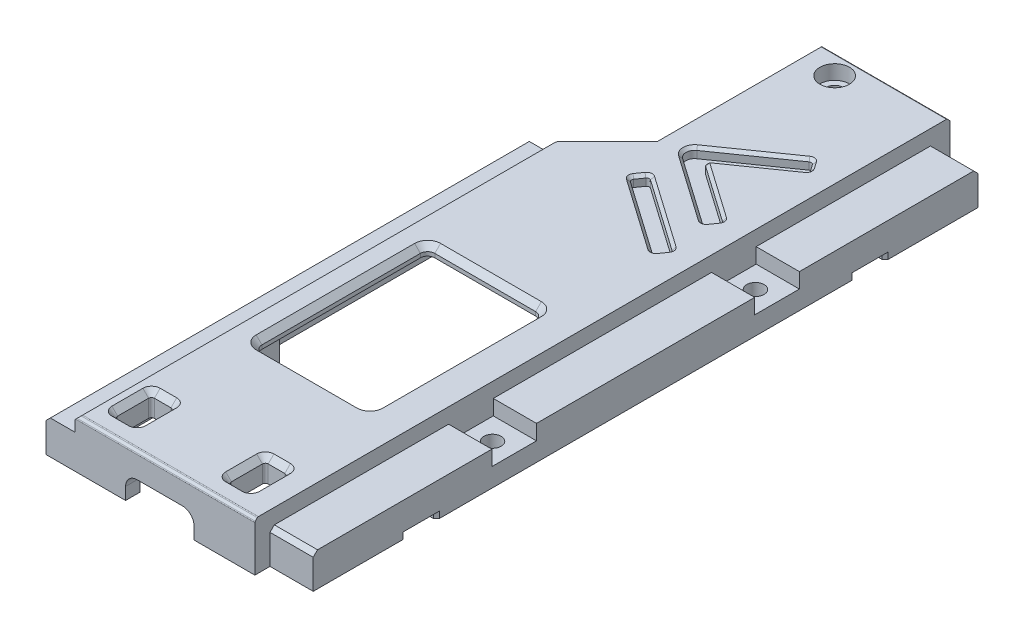
SolidWorks part; units mm, degrees
ref_plane "前视基准面" through (0, 0, 0) normal (0, 0, 1) x (1, 0, 0)
ref_plane "上视基准面" through (0, 0, 0) normal (0, 1, 0) x (1, 0, 0)
ref_plane "右视基准面" through (0, 0, 0) normal (1, 0, 0) x (0, 0, -1)
sketch "草图1" plane through (0, 0, 0) normal (0, 1, 0) x (1, 0, 0)
  line L1 (0, 0) -> (35, 0)
  line L2 (0, 0) -> (0, 96.5)
  line L3 (0, 96.5) -> (35, 96.5)
  line L4 (35, 0) -> (35, 96.5)
  point P1 (35, 96.5)
  dimension "D1" = 35
  dimension "D2" = 96.5
extrude "凸台-拉伸1" add sketch "草图1" along normal blind 6.8
sketch "草图10" plane through (0, 0, 0) normal (0, -1, 0) x (1, 0, 0)
  line L0 (3, -57.9) -> (3, -27)
  line L2 (3, -27) -> (5.4, -27)
  line L3 (3, -20) -> (3, -2)
  line L9 (26.2, -2) -> (3, -2)
  line L10 (5.4, -20) -> (5.4, -27)
  line L11 (3, -57.9) -> (26.2, -57.9)
  line L12 (3, -20) -> (5.4, -20)
  line L17 (26.2, -57.9) -> (26.2, -2)
  line L18 (0, 0) -> (35, 0) construction
  line L19 (3, -69.8559) -> (28.6, -69.8559) construction
  line L20 (3, -69.8559) -> (3, -2) construction
  line L21 (3, -2) -> (28.6, -2) construction
  line L22 (28.6, -69.8559) -> (28.6, -2) construction
  line L23 (0, -96.5) -> (0, 0) construction
  dimension "D2" = 2.4
  dimension "D3" = 55.9
  dimension "D4" = 18
  dimension "D5" = 25
  dimension "D7" = 2
  dimension "D8" = 25.6
  dimension "D9" = 3
  dimension "D1" = 2.4
extrude "切除-拉伸6" cut sketch "草图10" against normal blind 3.4
sketch "草图11" plane through (0, 0, 0) normal (0, 0, 1) x (1, 0, 0)
  line L0 (0, 0) -> (47, 0) construction
  line L1 (11.05, 0) -> (20.55, 0)
  line L2 (11.05, 0) -> (11.05, 1.7)
  line L3 (12.65, 3.3) -> (18.95, 3.3)
  line L4 (20.55, 1.7) -> (20.55, 0)
  line L7 (0, 6.8) -> (0, 0) construction
  arc A0 (18.95, 3.3) -> (20.55, 1.7) centre (18.95, 1.7) cw
  arc A1 (11.05, 1.7) -> (12.65, 3.3) centre (12.65, 1.7) cw
  dimension "D4" = 1.6
  dimension "D1" = 9.5
  dimension "D2" = 3.3
  dimension "D3" = 11.05
extrude "切除-拉伸7" cut sketch "草图11" against normal up to next
sketch "草图13" plane through (0, 3.4, 0) normal (0, -1, 0) x (1, 0, 0)
  line L1 (7.8, -21.18) -> (23.8, -21.18)
  line L2 (7.8, -21.18) -> (7.8, -45.18)
  line L3 (7.8, -45.18) -> (23.8, -45.18)
  line L4 (23.8, -21.18) -> (23.8, -45.18)
  line L5 (0, 0) -> (35, 0) construction
  line L6 (0, -96.5) -> (0, 0) construction
  dimension "D1" = 7.8
  dimension "D2" = 16
  dimension "D3" = 24
  dimension "D4" = 21.18
extrude "切除-拉伸9" cut sketch "草图13" against normal blind 10
sketch "草图24" plane through (0, 6.8, 0) normal (0, 1, 0) x (1, 0, 0)
  line L0 (0, 0) -> (35, 0) construction
  line L1 (6.35, 8.3) -> (9.45, 8.3)
  line L2 (6.35, 8.3) -> (6.35, 3.2)
  line L3 (6.35, 3.2) -> (9.45, 3.2)
  line L4 (9.45, 8.3) -> (9.45, 3.2)
  line L5 (22.15, 8.3) -> (25.25, 8.3)
  line L6 (22.15, 8.3) -> (22.15, 3.2)
  line L7 (22.15, 3.2) -> (25.25, 3.2)
  line L8 (25.25, 8.3) -> (25.25, 3.2)
  line L12 (11.05, 2) -> (11.05, 0) construction
  line L13 (20.55, 2) -> (20.55, 0) construction
  dimension "D1" = 3.1
  dimension "D2" = 5.1
  dimension "D3" = 3.1
  dimension "D4" = 5.1
  dimension "D5" = 3.2
  dimension "D6" = 1.6
  dimension "D7" = 1.6
extrude "切除-拉伸17" cut sketch "草图24" against normal up to next
sketch "草图25" plane through (0, 3.4, 0) normal (0, -1, 0) x (1, 0, 0)
  line L0 (25.25, -8.3) -> (22.15, -8.3) construction
  line L1 (25.25, -3.2) -> (25.25, -8.3) construction
  line L2 (22.15, -3.2) -> (25.25, -3.2) construction
  line L3 (22.15, -8.3) -> (22.15, -3.2) construction
  line L4 (9.45, -8.3) -> (6.35, -8.3) construction
  line L5 (9.45, -3.2) -> (9.45, -8.3) construction
  line L6 (6.35, -3.2) -> (9.45, -3.2) construction
  line L7 (6.35, -8.3) -> (6.35, -3.2) construction
  line L8 (25.25, -8.3) -> (22.15, -8.3)
  line L9 (25.25, -3.2) -> (25.25, -8.3)
  line L10 (22.15, -3.2) -> (25.25, -3.2)
  line L11 (22.15, -8.3) -> (22.15, -3.2)
  line L12 (9.45, -8.3) -> (6.35, -8.3)
  line L13 (9.45, -3.2) -> (9.45, -8.3)
  line L14 (6.35, -3.2) -> (9.45, -3.2)
  line L15 (6.35, -8.3) -> (6.35, -3.2)
  line L16 (26.45, -9.5) -> (20.95, -9.5)
  line L17 (20.95, -9.5) -> (20.95, -2)
  line L18 (20.95, -2) -> (26.45, -2)
  line L19 (26.45, -2) -> (26.45, -9.5)
  line L20 (10.65, -9.5) -> (5.15, -9.5)
  line L21 (5.15, -9.5) -> (5.15, -2)
  line L22 (5.15, -2) -> (10.65, -2)
  line L23 (10.65, -2) -> (10.65, -9.5)
  dimension "D1" = 1.2
extrude "切除-拉伸21" cut sketch "草图25" against normal blind 0.18 and the other way through all
fillet "圆角3" radius 0.4 8 edges at (25.25, 5.19, -8.3) (25.25, 5.19, -3.2) (22.15, 5.19, -3.2) (22.15, 5.19, -8.3) (9.45, 5.19, -8.3) (9.45, 5.19, -3.2) (6.35, 5.19, -3.2) (6.35, 5.19, -8.3)
chamfer "倒角2" distance 0.8 angle 45 16 edges at (25.25, 6.8, -5.75) (25.1328, 6.8, -8.1828) (25.1328, 6.8, -3.3172) (23.7, 6.8, -8.3) (23.7, 6.8, -3.2) (22.2672, 6.8, -8.1828) (22.2672, 6.8, -3.3172) (22.15, 6.8, -5.75) (9.45, 6.8, -5.75) (9.3328, 6.8, -8.1828) (9.3328, 6.8, -3.3172) (7.9, 6.8, -8.3) (7.9, 6.8, -3.2) (6.4672, 6.8, -8.1828) (6.4672, 6.8, -3.3172) (6.35, 6.8, -5.75)
fillet "圆角4" radius 1 4 edges at (23.8, 5.1, -21.18) (23.8, 5.1, -45.18) (7.8, 5.1, -45.18) (7.8, 5.1, -21.18)
chamfer "倒角1" distance 0.8 angle 45 8 edges at (15.8, 6.8, -45.18) (23.8, 6.8, -33.18) (7.8, 6.8, -33.18) (15.8, 6.8, -21.18) (23.5071, 6.8, -44.8871) (8.0929, 6.8, -44.8871) (23.5071, 6.8, -21.4729) (8.0929, 6.8, -21.4729)
sketch "草图26" plane through (0, 6.8, 0) normal (0, 1, 0) x (1, 0, 0)
  line L0 (4, 66.5) -> (10.7071, 73.2071) construction
  line L1 (11, 73.9142) -> (11, 96.0172) construction
  line L2 (4, 66.5) -> (11, 73.5)
  line L3 (11, 73.5) -> (11, 96.5)
  line L4 (0, 96.5) -> (0, 0) construction
  line L5 (35, 96.5) -> (0, 96.5) construction
  line L6 (0, 96.5) -> (0, 66.5)
  line L7 (11, 96.5) -> (0, 96.5)
  line L8 (4, 66.5) -> (0, 66.5)
extrude "切除-拉伸18" cut sketch "草图26" against normal up to next
sketch "草图28" plane through (0, 6.8, 0) normal (0, 1, 0) x (1, 0, 0)
  line L1 (0, 0) -> (4, 0)
  line L2 (0, 0) -> (0, 66.5)
  line L3 (0, 66.5) -> (4, 66.5)
  line L4 (4, 0) -> (4, 66.5)
extrude "切除-拉伸19" cut sketch "草图28" against normal blind 2.1
fillet "圆角5" radius 1 1 edges at (4, 5.75, -66.5)
chamfer "倒角3" distance 0.6 angle 45 4 edges at (11, 6.8, -85) (7.6464, 6.8, -70.1464) (4, 6.8, -33.0429) (4.0761, 6.8, -66.4685)
sketch "草图29" plane through (0, 3.4, 0) normal (0, -1, 0) x (1, 0, 0)
  line L0 (26.1, -48.179) -> (26.1, -18.179)
  line L1 (23.6, -15.679) -> (8, -15.679)
  line L2 (5.5, -18.179) -> (5.5, -48.179)
  line L3 (8, -50.679) -> (23.6, -50.679)
  line L4 (23.6, -16.679) -> (8, -16.679)
  line L5 (25.1, -48.179) -> (25.1, -18.179)
  line L6 (8, -49.679) -> (23.6, -49.679)
  line L7 (6.5, -18.179) -> (6.5, -48.179)
  line L8 (23.6, -16.679) -> (8, -16.679) construction
  line L9 (25.1, -48.179) -> (25.1, -18.179) construction
  line L10 (8, -49.679) -> (23.6, -49.679) construction
  line L11 (6.5, -18.179) -> (6.5, -48.179) construction
  arc A0 (23.6, -50.679) -> (26.1, -48.179) centre (23.6, -48.179) ccw
  arc A1 (26.1, -18.179) -> (23.6, -15.679) centre (23.6, -18.179) ccw
  arc A2 (8, -15.679) -> (5.5, -18.179) centre (8, -18.179) ccw
  arc A3 (5.5, -48.179) -> (8, -50.679) centre (8, -48.179) ccw
  arc A4 (25.1, -18.179) -> (23.6, -16.679) centre (23.6, -18.179) ccw
  arc A5 (23.6, -49.679) -> (25.1, -48.179) centre (23.6, -48.179) ccw
  arc A6 (6.5, -48.179) -> (8, -49.679) centre (8, -48.179) ccw
  arc A7 (8, -16.679) -> (6.5, -18.179) centre (8, -18.179) ccw
  arc A8 (25.1, -18.179) -> (23.6, -16.679) centre (23.6, -18.179) ccw construction
  arc A9 (23.6, -49.679) -> (25.1, -48.179) centre (23.6, -48.179) ccw construction
  arc A10 (6.5, -48.179) -> (8, -49.679) centre (8, -48.179) ccw construction
  arc A11 (8, -16.679) -> (6.5, -18.179) centre (8, -18.179) ccw construction
  dimension "D1" = 0
  dimension "D2" = 1
extrude "切除-拉伸20" cut sketch "草图29" against normal blind 2.06
chamfer "倒角4" distance 0.6 angle 45 2 edges at (0, 4.7, -33.25) (11, 0, -85)
sketch "草图30" plane through (0, 0, 0) normal (0, -1, 0) x (1, 0, 0)
  line L0 (28.6, -68.5) -> (28.6, -88.5) construction
  line L1 (12.5, -88.5) -> (12.5, -67.9) construction
  line L2 (28.6, -57.9) -> (28.6, -88.5) construction
  line L3 (12.5, -88.5) -> (12.5, -76.5)
  line L5 (35, -96.5) -> (11.6, -96.5) construction
  line L12 (12.5, -76.5) -> (12.5, -88.5) construction
  line L15 (3, -57.9) -> (26.2, -57.9) construction
  line L16 (3, -57.9) -> (28.6, -57.9)
  line L17 (28.6, -88.5) -> (28.6, -57.9)
  line L19 (28.6, -88.5) -> (12.5, -88.5)
  line L21 (12.5, -76.5) -> (3, -76.5)
  line L22 (3, -76.5) -> (3, -57.9)
  point P3 (28.6, -88.3067)
  point P6 (0, 0)
  point P7 (0, 0)
  point P8 (0, 0)
  point P9 (14.1823, -76.5)
  point P11 (0, 0)
  point P12 (0, 0)
  point P13 (12.5, -90.5404)
  point P15 (12.5, -88.6133)
  point P19 (0, 0)
  point P21 (0, 0)
  point P22 (0, 0)
  point P23 (0, 0)
  dimension "D1" = 12
  dimension "D2" = 8
extrude "切除-拉伸22" cut sketch "草图30" against normal blind 4
sketch "草图31" plane through (0, 6.8, 0) normal (0, 1, 0) x (1, 0, 0)
  line L0 (24.5128, 59.7234) -> (25.66, 61.3617)
  line L1 (12.66, 59.7234) -> (25.66, 59.7234) construction
  line L2 (12.66, 59.7234) -> (12.66, 82) construction
  line L3 (12.66, 82) -> (25.66, 82) construction
  line L4 (25.66, 59.7234) -> (25.66, 82) construction
  line L5 (24.5128, 59.7234) -> (13.8639, 67.1799)
  line L6 (25.66, 61.3617) -> (15.011, 68.8182)
  line L7 (13.8639, 67.1799) -> (15.011, 68.8182)
  line L8 (24.5128, 66.7234) -> (13.6042, 74.3617)
  line L9 (13.6042, 74.3617) -> (24.5128, 82)
  line L10 (24.5128, 82) -> (25.66, 80.3617)
  line L11 (25.66, 80.3617) -> (17.0911, 74.3617)
  line L12 (17.0911, 74.3617) -> (25.66, 68.3617)
  line L13 (25.66, 68.3617) -> (24.5128, 66.7234)
  line L14 (35, 96.5) -> (11.6, 96.5) construction
  line L15 (4, 0) -> (4, 66.0858) construction
  dimension "D1" = 2
  dimension "D2" = 55
  dimension "D3" = 55
  dimension "D4" = 0
  dimension "D5" = 0
  dimension "D6" = 0
  dimension "D7" = 13
  dimension "D8" = 7
  dimension "D9" = 2
  dimension "D10" = 2
  dimension "D11" = 90
  dimension "D12" = 12
  dimension "D13" = 0
  dimension "D14" = 0
  dimension "D15" = 13
  dimension "D16" = 14.5
  dimension "D17" = 8.66
extrude "切除-拉伸23" cut sketch "草图31" against normal blind 1.4
fillet "圆角6" radius 0.4 9 edges at (25.66, 6.1, -61.3617) (24.5128, 6.1, -59.7234) (15.011, 6.1, -68.8182) (13.8639, 6.1, -67.1799) (25.66, 6.1, -80.3617) (24.5128, 6.1, -82) (25.66, 6.1, -68.3617) (24.5128, 6.1, -66.7234) (17.0911, 6.1, -74.3617)
fillet "圆角7" radius 1.2 1 edges at (13.6042, 6.1, -74.3617)
chamfer "倒角5" distance 0.4 angle 45 20 edges at (21.4457, 6.8, -77.4108) (25.4968, 6.8, -80.3905) (17.3885, 6.8, -74.3617) (25.0864, 6.8, -81.1808) (21.4457, 6.8, -71.3126) (24.4841, 6.8, -81.8368) (25.4968, 6.8, -68.3329) (19.5966, 6.8, -78.5576) (25.0864, 6.8, -67.5425) (14.4964, 6.8, -74.3617) (24.4841, 6.8, -66.8866) (19.5966, 6.8, -70.1658) (20.3355, 6.8, -65.0899) (15.0398, 6.8, -68.655) (25.4968, 6.8, -61.3329) (14.4374, 6.8, -67.999) (25.0864, 6.8, -60.5425) (14.027, 6.8, -67.2087) (24.4841, 6.8, -59.8866) (19.1884, 6.8, -63.4516)
sketch "草图32" plane through (35, 0, 0) normal (1, 0, 0) x (0, 0, -1)
  line L0 (96.5, 6.8) -> (96.5, 0) construction
  line L1 (0, 6.8) -> (96.5, 6.8) construction
  line L2 (0, 6.8) -> (0, 0) construction
  line L3 (96.5, 6.8) -> (96.5, 0)
  line L4 (0, 6.8) -> (96.5, 6.8)
  line L5 (0, 6.8) -> (0, 0)
  line L6 (94.4, 4.7) -> (94.4, 0)
  line L7 (2.1, 4.7) -> (94.4, 4.7)
  line L8 (2.1, 4.7) -> (2.1, 0)
  line L9 (0, 0) -> (2.1, 0)
  line L10 (94.4, 0) -> (96.5, 0)
  dimension "D1" = 2.1
extrude "切除-拉伸24" cut sketch "草图32" against normal blind 6
chamfer "倒角6" distance 0.6 angle 45 2 edges at (32, 4.7, -94.4) (32, 4.7, -2.1)
chamfer "倒角7" distance 0.4 angle 45 2 edges at (20.3, 6.8, -96.5) (16.8, 6.8, 0)
fillet "圆角8" radius 0.2 4 edges at (20.1, 6.4, -96.5) (20.3, 6.8, -96.1) (16.8, 6.8, -0.4) (16.6, 6.4, 0)
sketch "草图34" plane through (0, 0, 0) normal (0, -1, 0) x (1, 0, 0)
  line L1 (35, -14.6) -> (35, -19.6)
  line L2 (35, -76.9) -> (35, -81.9)
  line L43 (35, -94.4) -> (35, -81.9)
  line L44 (35, -81.9) -> (34.6, -81.5)
  line L45 (34.6, -81.5) -> (33, -81.5)
  line L46 (33, -81.5) -> (31, -83.5)
  line L47 (33, -81.5) -> (31, -83.5)
  line L48 (31, -83.5) -> (30.8, -83.5)
  line L49 (30.8, -83.5) -> (30.8, -75.3)
  line L50 (30.8, -75.3) -> (31, -75.3)
  line L51 (31, -75.3) -> (33, -77.3)
  line L52 (31, -75.3) -> (33, -77.3)
  line L53 (33, -77.3) -> (34.6, -77.3)
  line L54 (34.6, -77.3) -> (35, -76.9)
  line L55 (35, -76.9) -> (35, -19.6)
  line L56 (35, -19.6) -> (34.6, -19.2)
  line L57 (34.6, -19.2) -> (33, -19.2)
  line L58 (33, -19.2) -> (31, -21.2)
  line L59 (33, -19.2) -> (31, -21.2)
  line L60 (31, -21.2) -> (30.8, -21.2)
  line L61 (30.8, -21.2) -> (30.8, -13)
  line L62 (30.8, -13) -> (31, -13)
  line L63 (31, -13) -> (33, -15)
  line L64 (31, -13) -> (33, -15)
  line L65 (33, -15) -> (34.6, -15)
  line L66 (34.6, -15) -> (35, -14.6)
  line L67 (35, -14.6) -> (35, -2.1)
  line L68 (35, -2.1) -> (29, -2.1)
  line L69 (29, -2.1) -> (29, 0)
  line L70 (29, 0) -> (0, 0)
  line L71 (0, 0) -> (0, -21.1)
  line L72 (0, -21.1) -> (-1, -21.1)
  line L73 (-1, -21.1) -> (-2, -22.1)
  line L74 (-2, -22.1) -> (-2, -74.4)
  line L75 (-2, -74.4) -> (-1, -75.4)
  line L76 (-1, -75.4) -> (0, -75.4)
  line L77 (0, -75.4) -> (0, -77.5)
  line L78 (0, -77.5) -> (11, -77.5)
  line L79 (11, -77.5) -> (11, -90.5)
  line L80 (11, -90.5) -> (19, -90.5)
  line L81 (19, -90.5) -> (19, -95.5)
  line L82 (19, -95.5) -> (20, -96.5)
  line L83 (20, -96.5) -> (29, -96.5)
  line L84 (29, -96.5) -> (29, -94.4)
  line L85 (29, -94.4) -> (35, -94.4)
  line L87 (35, -81.9) -> (34.6, -81.5)
  line L88 (34.6, -81.5) -> (33, -81.5)
  line L91 (31, -83.5) -> (30.8, -83.5)
  line L92 (30.8, -83.5) -> (30.8, -75.3)
  line L93 (30.8, -75.3) -> (31, -75.3)
  line L96 (33, -77.3) -> (34.6, -77.3)
  line L97 (34.6, -77.3) -> (35, -76.9)
  line L99 (35, -19.6) -> (34.6, -19.2)
  line L100 (34.6, -19.2) -> (33, -19.2)
  line L103 (31, -21.2) -> (30.8, -21.2)
  line L104 (30.8, -21.2) -> (30.8, -13)
  line L105 (30.8, -13) -> (31, -13)
  line L108 (33, -15) -> (34.6, -15)
  line L109 (34.6, -15) -> (35, -14.6)
  dimension "D1" = 0
sketch "草图36" plane through (35, 0, 0) normal (1, 0, 0) x (0, 0, -1)
  line L0 (69.5, 2.8) -> (69.5, 4.8) construction
  line L1 (63.5, 4.8) -> (63.5, 2.8) construction
  line L2 (33, 2.8) -> (33, 4.8) construction
  line L3 (27, 4.8) -> (27, 2.8) construction
  line L4 (69.5, 2.8) -> (69.5, 4.8) construction
  line L5 (63.5, 4.8) -> (63.5, 2.8) construction
  line L6 (33, 2.8) -> (33, 4.8) construction
  line L7 (27, 4.8) -> (27, 2.8) construction
  line L8 (27, 2.8) -> (33, 2.8) construction
  line L9 (63.5, 2.8) -> (69.5, 2.8) construction
  line L16 (26.9, 4.7) -> (33.1, 4.7)
  line L17 (63.4, 4.7) -> (69.6, 4.7)
  line L18 (26.9, 4.7) -> (26.9, 2.6)
  line L19 (26.9, 2.6) -> (33.1, 2.6)
  line L20 (33.1, 2.6) -> (33.1, 4.7)
  line L21 (63.4, 4.7) -> (63.4, 2.6)
  line L22 (63.4, 2.6) -> (69.6, 2.6)
  line L23 (69.6, 2.6) -> (69.6, 4.7)
  line L24 (2.7, 4.7) -> (93.8, 4.7) construction
  dimension "D1" = 0.1
  dimension "D2" = 0.1
  dimension "D3" = 0.2
  dimension "D4" = 0.1
extrude "切除-拉伸27" cut sketch "草图36" against normal blind 6
sketch "草图37" plane through (0, 0, 0) normal (0, -1, 0) x (1, 0, 0)
  line L0 (35, -14.6) -> (35, -19.6)
  line L1 (35, -76.9) -> (35, -81.9)
  line L39 (35, -94.4) -> (35, -81.9)
  line L40 (35, -81.9) -> (34.6, -81.5)
  line L41 (34.6, -81.5) -> (33, -81.5)
  line L42 (33, -81.5) -> (31, -83.5)
  line L43 (31, -83.5) -> (30.8, -83.5)
  line L44 (30.8, -83.5) -> (30.8, -75.3)
  line L45 (30.8, -75.3) -> (31, -75.3)
  line L46 (31, -75.3) -> (33, -77.3)
  line L47 (33, -77.3) -> (34.6, -77.3)
  line L48 (34.6, -77.3) -> (35, -76.9)
  line L49 (35, -76.9) -> (35, -19.6)
  line L50 (35, -19.6) -> (34.6, -19.2)
  line L51 (34.6, -19.2) -> (33, -19.2)
  line L52 (33, -19.2) -> (31, -21.2)
  line L53 (31, -21.2) -> (30.8, -21.2)
  line L54 (30.8, -21.2) -> (30.8, -13)
  line L55 (30.8, -13) -> (31, -13)
  line L56 (31, -13) -> (33, -15)
  line L57 (33, -15) -> (34.6, -15)
  line L58 (34.6, -15) -> (35, -14.6)
  line L59 (35, -14.6) -> (35, -2.1)
  line L60 (35, -2.1) -> (29, -2.1)
  line L61 (29, -2.1) -> (29, 0)
  line L62 (29, 0) -> (0, 0)
  line L63 (0, 0) -> (0, -21.1)
  line L64 (0, -21.1) -> (-1, -21.1)
  line L65 (-1, -21.1) -> (-2, -22.1)
  line L66 (-2, -22.1) -> (-2, -74.4)
  line L67 (-2, -74.4) -> (-1, -75.4)
  line L68 (-1, -75.4) -> (0, -75.4)
  line L69 (0, -75.4) -> (0, -77.5)
  line L70 (0, -77.5) -> (11, -77.5)
  line L71 (11, -77.5) -> (11, -90.5)
  line L72 (11, -90.5) -> (19, -90.5)
  line L73 (19, -90.5) -> (19, -95.5)
  line L74 (19, -95.5) -> (20, -96.5)
  line L75 (20, -96.5) -> (29, -96.5)
  line L76 (29, -96.5) -> (29, -94.4)
  line L77 (29, -94.4) -> (35, -94.4)
  line L79 (35, -81.9) -> (34.6, -81.5)
  line L80 (34.6, -81.5) -> (33, -81.5)
  line L81 (33, -81.5) -> (31, -83.5)
  line L82 (31, -83.5) -> (30.8, -83.5)
  line L83 (30.8, -83.5) -> (30.8, -75.3)
  line L84 (30.8, -75.3) -> (31, -75.3)
  line L85 (31, -75.3) -> (33, -77.3)
  line L86 (33, -77.3) -> (34.6, -77.3)
  line L87 (34.6, -77.3) -> (35, -76.9)
  line L89 (35, -19.6) -> (34.6, -19.2)
  line L90 (34.6, -19.2) -> (33, -19.2)
  line L91 (33, -19.2) -> (31, -21.2)
  line L92 (31, -21.2) -> (30.8, -21.2)
  line L93 (30.8, -21.2) -> (30.8, -13)
  line L94 (30.8, -13) -> (31, -13)
  line L95 (31, -13) -> (33, -15)
  line L96 (33, -15) -> (34.6, -15)
  line L97 (34.6, -15) -> (35, -14.6)
  dimension "D1" = 0
extrude "切除-拉伸28" cut sketch "草图37" against normal blind 0.9
sketch "草图38" plane through (0, 2.6, 0) normal (0, 1, 0) x (1, 0, 0)
  circle A0 centre (32, 30) radius 1.2 construction
  circle A1 centre (32, 66.5) radius 1.2 construction
  circle A2 centre (32, 30) radius 1.2
  circle A3 centre (32, 66.5) radius 1.2
extrude "切除-拉伸29" cut sketch "草图38" against normal through all
sketch "草图39" plane through (0, 6.8, 0) normal (0, 1, 0) x (1, 0, 0)
  circle A0 centre (16, 93.5) radius 1.5 construction
  circle A1 centre (16, 93.5) radius 1.5 construction
  circle A2 centre (16, 93.5) radius 1.2
  circle A3 centre (16, 93.5) radius 2.05
  dimension "D1" = 4.1
  dimension "D2" = 2.4
extrude "切除-拉伸30" cut sketch "草图39" against normal through all contours A2
extrude "切除-拉伸31" cut sketch "草图39<3>" against normal blind 2 contours A3
sketch "草图39<3>" plane through (0, 6.8, 0) normal (0, 1, 0) x (1, 0, 0) same geometry as "草图39"
sketch "草图40" plane through (0, 4, 0) normal (0, -1, 0) x (1, 0, 0)
  line L0 (12.5, -76.5) -> (12.5, -88.5) construction
  line L1 (28.6, -88.5) -> (12.5, -88.5)
  line L2 (28.6, -88.5) -> (28.6, -86.8)
  line L3 (28.6, -86.8) -> (12.5, -86.8)
  line L4 (12.5, -88.5) -> (12.5, -86.8)
  dimension "D1" = 1.7
extrude "凸台-拉伸2" add sketch "草图40" along normal offset from surface (3.5 mm away) 0.5 up to face at (16, 0, -92.3)
